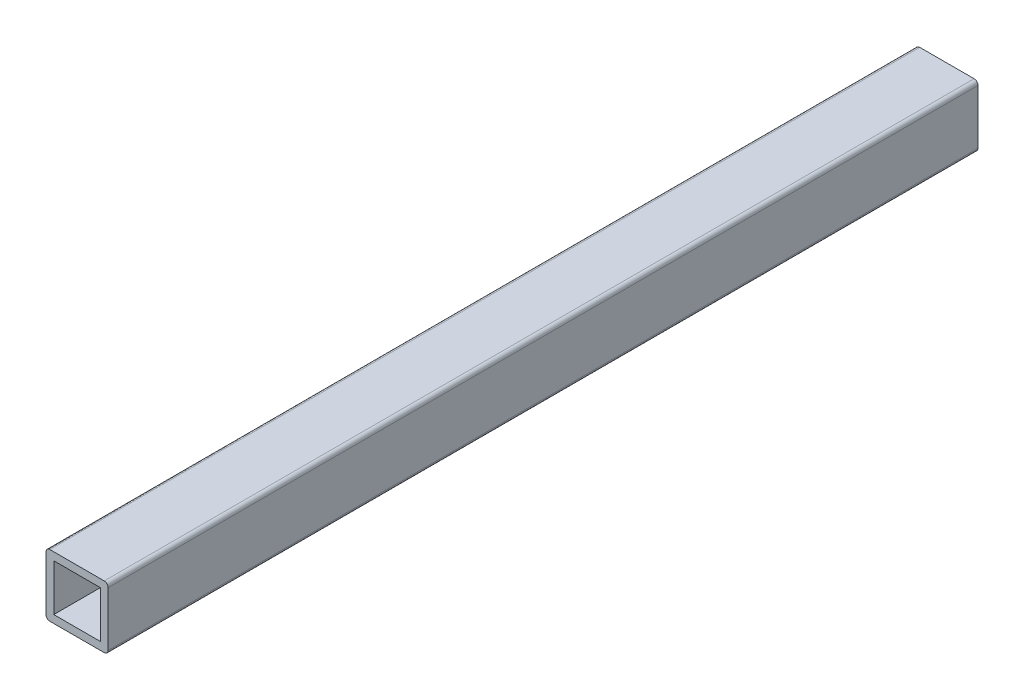
SolidWorks part; units mm, degrees
ref_plane "Front Plane" through (0, 0, 0) normal (0, 0, 1) x (1, 0, 0)
ref_plane "Top Plane" through (0, 0, 0) normal (0, 1, 0) x (1, 0, 0)
ref_plane "Right Plane" through (0, 0, 0) normal (1, 0, 0) x (0, 0, -1)
sketch "Sketch1" plane through (0, 0, 0) normal (0, 0, 1) x (1, 0, 0)
  line L0 (-4.7625, -4.7625) -> (-4.7625, 4.7625)
  line L1 (-6.35, -6.35) -> (6.35, -6.35)
  line L2 (-6.35, -6.35) -> (-6.35, 6.35)
  line L3 (-6.35, 6.35) -> (6.35, 6.35)
  line L4 (6.35, -6.35) -> (6.35, 6.35)
  line L5 (-6.35, -6.35) -> (6.35, 6.35) construction
  line L6 (-6.35, 6.35) -> (6.35, -6.35) construction
  line L7 (-4.7625, 4.7625) -> (4.7625, 4.7625)
  line L8 (4.7625, -4.7625) -> (4.7625, 4.7625)
  line L9 (-4.7625, -4.7625) -> (4.7625, -4.7625)
  point P0 (0, 0)
  point P10 (-4.7625, -6.35)
  dimension "Outside Width" = 12.7
  dimension "Outside Height" = 12.7
  dimension "Wall Thickness" = 1.5875
sketch "Sketch2" plane through (0, 0, 0) normal (1, 0, 0) x (0, 0, -1)
  line L0 (-88.9, 6.35) -> (88.9, 6.35) construction
  point P2 (0, 6.35)
  point P3 (-76.2, 6.35)
  point P5 (76.2, 6.35)
  dimension "Length" = 177.8
  dimension "D1" = 12.7
  dimension "D2" = 12.7
extrude "Boss-Extrude1" add sketch "Sketch1" along normal up to vertex (88.9 mm away) and the other way up to vertex (88.9 mm away) up to point (0, 6.35, 88.9) other way up to point (0, 6.35, -88.9)
fillet "Fillet1" radius 0.7937 4 edges at (6.35, 6.35, 0) (-6.35, 6.35, 0) (-6.35, -6.35, 0) (6.35, -6.35, 0)
ref_axis "Center Axis 1" through (0, 0, -1005.84) along (0, 0, 1)
equation "\"D1@Fillet1\"=\"Wall Thickness@Sketch1\"/2"
equation "\"D1@Sketch2\"=\"Outside Width@Sketch1\""
equation "\"D2@Sketch2\"=\"D1@Sketch2\""
